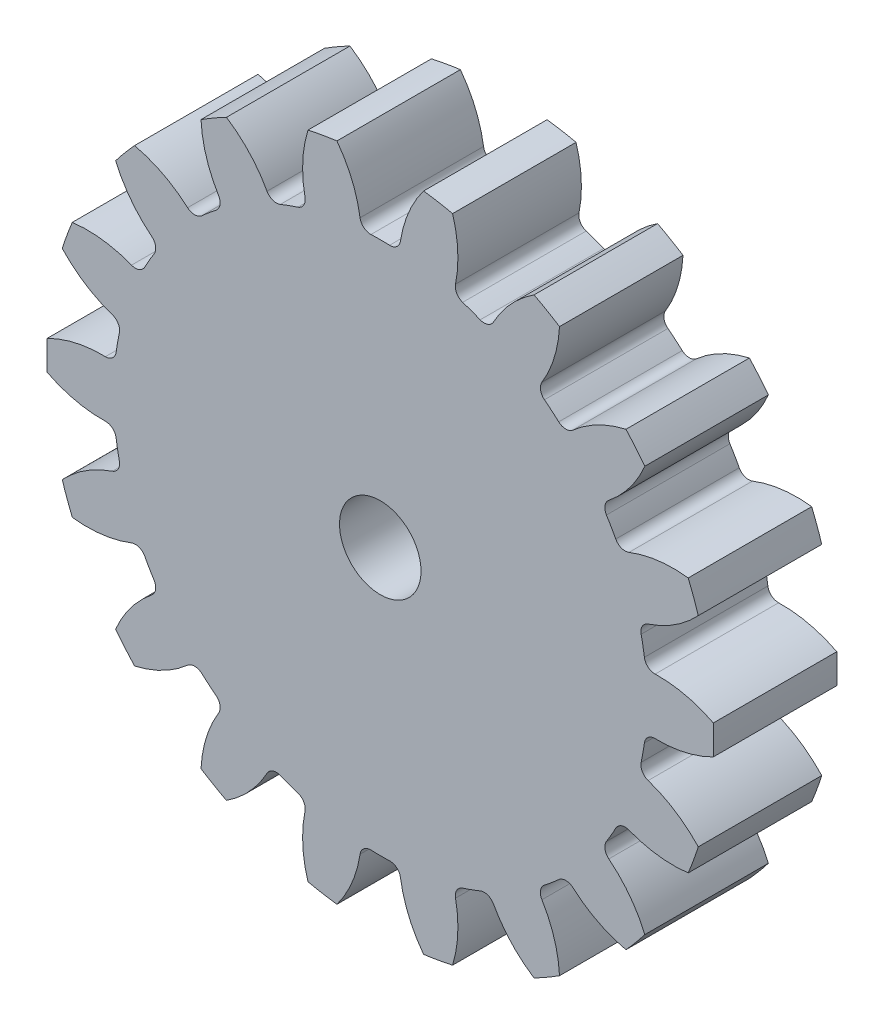
SolidWorks part; units mm, degrees
ref_plane "Front" through (0, 0, 0) normal (0, 0, 1) x (1, 0, 0)
ref_plane "Top" through (0, 0, 0) normal (0, 1, 0) x (1, 0, 0)
ref_plane "Right" through (0, 0, 0) normal (1, 0, 0) x (0, 0, -1)
sketch "Sketch1" plane through (0, 0, 0) normal (0, 0, 1) x (1, 0, 0)
  circle A0 centre (0, 0) radius 10.8
  circle A1 centre (0, 0) radius 13.5
  circle A2 centre (0, 0) radius 12.15
  dimension "D1" = 27
  dimension "D2" = 21.6
  dimension "D3" = 24.3
extrude "Boss-Extrude1" add sketch "Sketch1" along normal mid plane 5 contours A1
sketch "Sketch3" plane through (0, 0, 0) normal (0, 0, 1) x (1, 0, 0)
  line L0 (0, 0) -> (0, 13.5) construction
  line L1 (0, 0) -> (-0.7745, 10.7722) construction
  line L2 (-1.0589, 12.1038) -> (1.0589, 12.1038) construction
  line L3 (-1.5353, 13.4124) -> (0, 9.1943) construction
  line L4 (1.0589, 12.1038) -> (3.1447, 11.736) construction
  line L5 (2.3443, 13.2949) -> (0, 0) construction
  arc A0 (-0.7745, 10.7722) -> (0.7745, 10.7722) centre (0, 0) cw
  arc A4 (1.7552, 13.3854) -> (-1.7552, 13.3854) centre (0, 0) ccw
  circle A5 centre (0, 0) radius 13.5 construction
  arc A7 (-1.7552, 13.3854) -> (-0.7745, 10.7722) centre (-5.6881, 10.4189) cw
  arc A10 (1.7552, 13.3854) -> (0.7745, 10.7722) centre (5.6881, 10.4189) ccw
  circle A11 centre (0, 0) radius 10.8 construction
  circle A12 centre (0, 0) radius 12.15 construction
  dimension "D1" = 20
  dimension "D2" = 10
extrude "Cut-Extrude1" cut sketch "Sketch3" against normal through all both and the other way through all contours A10 A4 A7 A0 region at (0, 12.324, 0)
fillet "Fillet2" radius 0.43 2 edges at (-0.7745, 10.7722, 0) (0.7745, 10.7722, 0)
pattern_circular "CirPattern1" count 18 over 360 about axis through (0, 0, 2.5) along (0, 0, -1) of "Cut-Extrude1", "Fillet2"
sketch "Sketch4" plane through (0, 0, 0) normal (0, 0, 1) x (1, 0, 0)
  circle A0 centre (0, 0) radius 1.65
  dimension "D1" = 3.3
extrude "Through_Center_Hole" cut sketch "Sketch4" against normal through all both and the other way through all
equation "\"od\"= 27'outside diameter"
equation "\"n\"= 18'number of teeth"
equation "\"m\"= \"od\" / ( \"n\" + 2 )'module"
equation "\"p\"= \"m\" * pi'pitch"
equation "\"d\"= \"m\" * \"n\"'primitive diameter"
equation "\"da\"= \"d\" + 2 * \"m\"'head diamater"
equation "\"df\"= \"d\" - 2 * \"m\"'foot diameter"
equation "\"D1@Sketch1\"=\"od\""
equation "\"D2@Sketch1\"=\"df\""
equation "\"D3@Sketch1\"=\"d\""
equation "\"D2@Sketch3\"=180/\"n\""
equation "\"D1@CirPattern1\"=\"n\""
